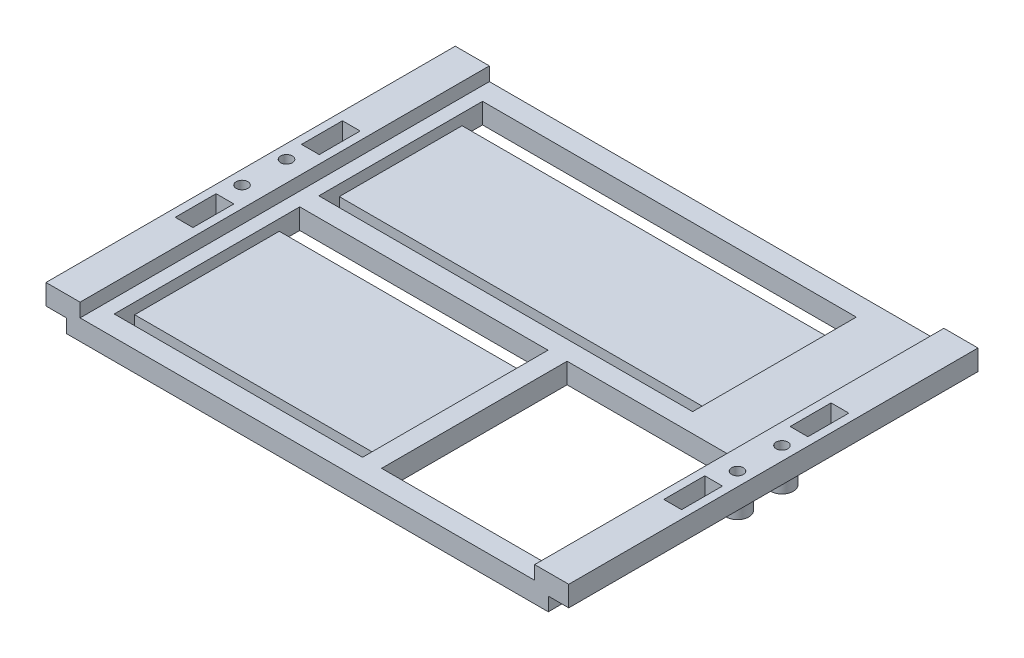
SolidWorks part; units mm, degrees
ref_plane "Front Plane" through (0, 0, 0) normal (0, 0, 1) x (1, 0, 0)
ref_plane "Top Plane" through (0, 0, 0) normal (0, 1, 0) x (1, 0, 0)
ref_plane "Right Plane" through (0, 0, 0) normal (1, 0, 0) x (0, 0, -1)
sketch "Sketch2" plane through (0, 0, 0) normal (0, 0, 1) x (1, 0, 0)
  line L0 (179.1, 12.5) -> (191.6, 12.5)
  line L1 (7.5, 0) -> (184.1, 0)
  line L2 (0, 5) -> (0, 12.5)
  line L3 (0, 12.5) -> (12.5, 12.5)
  line L4 (191.6, 5) -> (191.6, 12.5)
  line L7 (0, 5) -> (7.5, 5)
  line L8 (7.5, 0) -> (7.5, 5)
  line L11 (191.6, 5) -> (184.1, 5)
  line L12 (184.1, 0) -> (184.1, 5)
  line L14 (12.5, 12.5) -> (12.5, 7.5)
  line L15 (12.5, 7.5) -> (179.1, 7.5)
  line L16 (179.1, 12.5) -> (179.1, 7.5)
  dimension "D1" = 191.6
  dimension "D2" = 5
  dimension "D3" = 5
  dimension "D4" = 5
  dimension "D5" = 12.5
  dimension "D6" = 7.5
  dimension "D7" = 7.5
  dimension "D8" = 12.5
  dimension "D9" = 12.5
extrude "PlateFrame" add sketch "Sketch2" along normal blind 150
sketch "Sketch3" plane through (0, 12.5, 0) normal (0, 1, 0) x (1, 0, 0)
  line L0 (12.5, 0) -> (0, 0) construction
  line L2 (0, -150) -> (0, 0) construction
  line L3 (191.6, -150) -> (191.6, 0) construction
  line L4 (191.6, 0) -> (179.1, 0) construction
  circle A0 centre (5, -66.85) radius 2.15
  circle A1 centre (5, -83.15) radius 2.15
  circle A2 centre (186.6, -66.85) radius 2.15
  circle A3 centre (186.6, -83.15) radius 2.15
  dimension "D1" = 4.3
  dimension "D2" = 4.3
  dimension "D3" = 4.3
  dimension "D4" = 4.3
  dimension "D5" = 66.85
  dimension "D6" = 16.3
  dimension "D7" = 5
  dimension "D8" = 5
  dimension "D9" = 5
  dimension "D10" = 181.6
  dimension "D11" = 66.85
  dimension "D12" = 16.3
extrude "HoleSupport" cut sketch "Sketch3" against normal blind 7.5
sketch "Sketch4" plane through (0, 12.5, 0) normal (0, 1, 0) x (1, 0, 0)
  circle A0 centre (5, -66.85) radius 2.15
  circle A1 centre (5, -83.15) radius 2.15
  circle A2 centre (186.6, -83.15) radius 2.15
  circle A3 centre (186.6, -66.85) radius 2.15
  circle A4 centre (186.6, -66.85) radius 4.15
  circle A5 centre (186.6, -83.15) radius 4.15
  circle A6 centre (5, -66.85) radius 4.15
  circle A7 centre (5, -83.15) radius 4.15
  dimension "D1" = 2
extrude "CylindricalSupports" add sketch "Sketch4" against normal blind 12.5
sketch "Sketch8" plane through (0, 7.5, 0) normal (0, 1, 0) x (1, 0, 0)
  line L0 (12.5, -150) -> (12.5, 0) construction
  line L2 (154.5, -7.5) -> (17.5, -7.5)
  line L3 (154.5, -7.5) -> (154.5, -67.5)
  line L4 (154.5, -67.5) -> (17.5, -67.5)
  line L5 (17.5, -7.5) -> (17.5, -67.5)
  line L6 (108.5, -142.5) -> (17.5, -142.5)
  line L7 (108.5, -142.5) -> (108.5, -74.5)
  line L8 (108.5, -74.5) -> (17.5, -74.5)
  line L9 (17.5, -142.5) -> (17.5, -74.5)
  line L10 (179.1, 0) -> (12.5, 0) construction
  line L11 (179.1, -150) -> (12.5, -150) construction
  dimension "D1" = 5
  dimension "D2" = 7.5
  dimension "D3" = 7.5
  dimension "D4" = 5
  dimension "D5" = 60
  dimension "D6" = 68
  dimension "D7" = 137
  dimension "D8" = 91
extrude "ItemLayout" cut sketch "Sketch8" against normal blind 4
sketch "Sketch9" plane through (0, 7.5, 0) normal (0, 1, 0) x (1, 0, 0)
  line L0 (179.1, -150) -> (179.1, 0) construction
  line L1 (115.5, -74.5) -> (174.1, -74.5)
  line L2 (115.5, -74.5) -> (115.5, -142.5)
  line L3 (115.5, -142.5) -> (174.1, -142.5)
  line L4 (174.1, -74.5) -> (174.1, -142.5)
  line L5 (179.1, -150) -> (12.5, -150) construction
  line L7 (108.5, -142.5) -> (108.5, -74.5) construction
  dimension "D1" = 5
  dimension "D2" = 7.5
  dimension "D3" = 68
  dimension "D4" = 7
extrude "HoleCutout" cut sketch "Sketch9" against normal blind 7.5
sketch "Sketch10" plane through (0, 3.5, 0) normal (0, 1, 0) x (1, 0, 0)
  line L0 (108.5, -142.5) -> (108.5, -74.5) construction
  line L1 (17.5, -74.5) -> (108.5, -74.5)
  line L2 (17.5, -74.5) -> (17.5, -82)
  line L3 (17.5, -82) -> (108.5, -82)
  line L4 (108.5, -74.5) -> (108.5, -82)
  line L5 (108.5, -142.5) -> (108.5, -74.5) construction
  line L6 (17.5, -142.5) -> (108.5, -142.5)
  line L7 (17.5, -142.5) -> (17.5, -135)
  line L8 (17.5, -135) -> (108.5, -135)
  line L9 (108.5, -142.5) -> (108.5, -135)
  line L10 (154.5, -67.5) -> (154.5, -7.5) construction
  line L11 (17.5, -7.5) -> (154.5, -7.5)
  line L12 (17.5, -7.5) -> (17.5, -15)
  line L13 (17.5, -15) -> (154.5, -15)
  line L14 (154.5, -7.5) -> (154.5, -15)
  line L16 (17.5, -67.5) -> (154.5, -67.5)
  line L17 (17.5, -67.5) -> (17.5, -60)
  line L18 (17.5, -60) -> (154.5, -60)
  line L19 (154.5, -67.5) -> (154.5, -60)
  dimension "D1" = 7.5
  dimension "D2" = 7.5
  dimension "D3" = 7.5
  dimension "D4" = 7.5
extrude "VelcroCut" cut sketch "Sketch10" against normal blind 3.5
sketch "Sketch11" plane through (0, 12.5, 0) normal (0, 1, 0) x (1, 0, 0)
  line L0 (12.5, -150) -> (12.5, 0) construction
  line L1 (9.5, -59.35) -> (3, -59.35)
  line L2 (9.5, -59.35) -> (9.5, -44.35)
  line L3 (9.5, -44.35) -> (3, -44.35)
  line L4 (3, -59.35) -> (3, -44.35)
  line L5 (188.6, -59.35) -> (182.1, -59.35)
  line L6 (188.6, -59.35) -> (188.6, -44.35)
  line L7 (188.6, -44.35) -> (182.1, -44.35)
  line L8 (182.1, -59.35) -> (182.1, -44.35)
  line L9 (182.1, -90.65) -> (188.6, -90.65)
  line L10 (182.1, -90.65) -> (182.1, -105.65)
  line L11 (182.1, -105.65) -> (188.6, -105.65)
  line L12 (188.6, -90.65) -> (188.6, -105.65)
  line L13 (3, -90.65) -> (9.5, -90.65)
  line L14 (3, -90.65) -> (3, -105.65)
  line L15 (3, -105.65) -> (9.5, -105.65)
  line L16 (9.5, -90.65) -> (9.5, -105.65)
  line L17 (12.5, -150) -> (12.5, 0) construction
  line L18 (179.1, -150) -> (179.1, 0) construction
  line L19 (179.1, -150) -> (179.1, 0) construction
  circle A0 centre (5, -83.15) radius 2.15 construction
  circle A1 centre (5, -66.85) radius 2.15 construction
  circle A2 centre (186.6, -66.85) radius 2.15 construction
  circle A3 centre (186.6, -83.15) radius 2.15 construction
  dimension "D2" = 7.5
  dimension "D12" = 7.5
  dimension "D1" = 7.5
  dimension "D3" = 3
  dimension "D4" = 3
  dimension "D5" = 6.5
  dimension "D6" = 15
  dimension "D7" = 6.5
  dimension "D8" = 15
  dimension "D9" = 3
  dimension "D10" = 3
  dimension "D11" = 7.5
  dimension "D13" = 15
  dimension "D14" = 15
  dimension "D15" = 6.5
  dimension "D16" = 6.5
extrude "Cut-Extrude1" cut sketch "Sketch11" against normal blind 12.5
